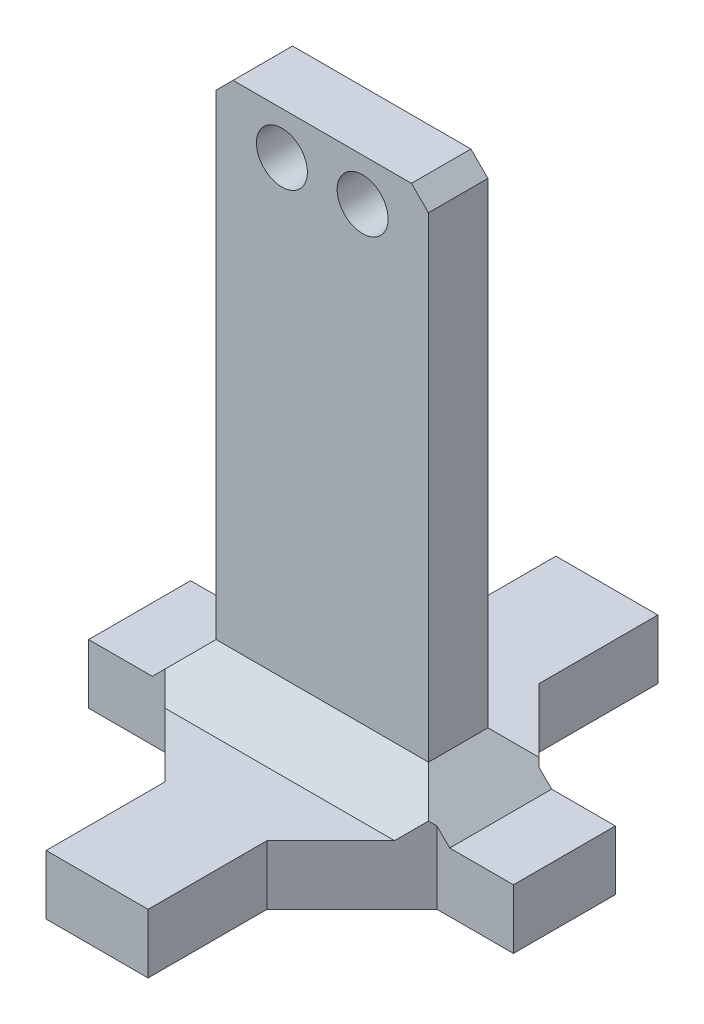
SolidWorks part; units mm, degrees
ref_plane "Front Plane" through (0, 0, 0) normal (0, 0, 1) x (1, 0, 0)
ref_plane "Top Plane" through (0, 0, 0) normal (0, 1, 0) x (1, 0, 0)
ref_plane "Right Plane" through (0, 0, 0) normal (1, 0, 0) x (0, 0, -1)
sketch "Sketch1" plane through (0, 0, 0) normal (0, 0, 1) x (1, 0, 0)
  line L0 (7.75, 65) -> (17.25, 65) construction
  line L1 (0, 0) -> (25, 0)
  line L2 (0, 0) -> (0, 70)
  line L3 (0, 70) -> (25, 70)
  line L4 (25, 0) -> (25, 70)
  circle A0 centre (7.75, 65) radius 3
  circle A1 centre (17.25, 65) radius 3
  point P7 (12.5, 65)
  point P8 (12.5, 70)
  point P11 (0, 0)
  point P12 (17.25, 65)
  point P13 (25, 70)
  dimension "D1" = 6
  dimension "D2" = 9.5
  dimension "D3" = 65
  dimension "D4" = 25
  dimension "D5" = 5
extrude "Boss-Extrude1" add sketch "Sketch1" along normal blind 7
sketch "Sketch2" plane through (0, 0, 0) normal (0, -1, 0) x (1, 0, 0)
  line L0 (0, 7) -> (0, 0) construction
  line L1 (6.5, 33.5) -> (18.5, 33.5)
  line L2 (6.5, 33.5) -> (6.5, -26.5)
  line L3 (6.5, -26.5) -> (18.5, -26.5)
  line L4 (18.5, 33.5) -> (18.5, -26.5)
  line L5 (-12.5, 9.5) -> (37.5, 9.5)
  line L6 (-12.5, 9.5) -> (-12.5, -2.5)
  line L7 (-12.5, -2.5) -> (37.5, -2.5)
  line L8 (37.5, 9.5) -> (37.5, -2.5)
  line L9 (0, 7) -> (25, 7) construction
  point P8 (0, 3.5)
  point P9 (-12.5, 3.5)
  point P12 (12.5, 33.5)
  point P13 (12.5, 7)
  point P14 (12.5, 9.5)
  point P17 (0, 0)
  point P18 (6.5, 3.5)
  point P19 (0, 0)
  line M5 (0, 0) -> (25, 0)
  line M6 (25, 0) -> (25, 7)
  line M7 (25, 7) -> (0, 7)
  line M8 (0, 7) -> (0, 0)
  dimension "D1" = 12
  dimension "D2" = 12
  dimension "D3" = 60
  dimension "D4" = 50
extrude "Boss-Extrude2" add sketch "Sketch2" against normal blind 7 contours L2 L5 L4 L1 | L6 L7 L2 L5 M5 M8 M7 | L4 L2 M7 M5 | L8 L5 L4 L7 M7 M6 M5 | L7 L2 L3 L4 | L2 M7 M8 M5 | L5 L2 L4 M7 | L2 L7 L4 M5 | L4 M7 M5 M6 region at (12.5, 0, 21.5) region at (12.5, 0, 8.25) region at (-4.5582, 0, 3.5) region at (29.5582, 0, 3.5) region at (12.5, 0, 3.5) region at (3.25, 0, 3.5) region at (21.75, 0, 3.5) region at (12.5, 0, -1.25) region at (12.5, 0, -14.5)
chamfer "Chamfer2" distance 10 angle 45 4 edges at (6.5, 3.5, 9.5) (6.5, 3.5, -2.5) (18.5, 3.5, -2.5) (18.5, 3.5, 9.5)
chamfer "Chamfer3" distance 5 angle 45 2 edges at (12.5, 7, 7) (12.5, 7, 0)
chamfer "Chamfer4" distance 5 angle 45 2 edges at (25, 7, 3.5) (0, 7, 3.5)
chamfer "Chamfer5" distance 2 angle 45 2 edges at (0, 70, 3.5) (25, 70, 3.5)
